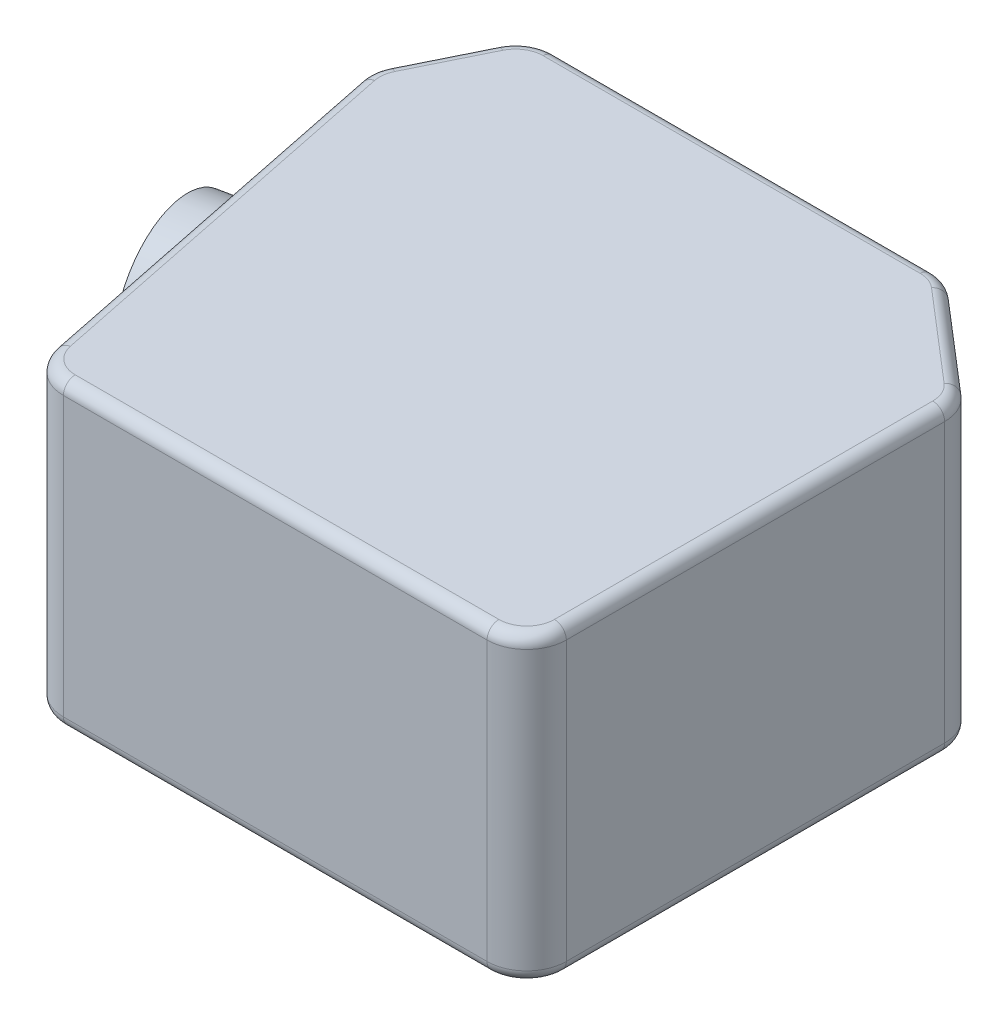
SolidWorks part; units mm, degrees
ref_plane "Front Plane" through (0, 0, 0) normal (0, 0, 1) x (1, 0, 0)
ref_plane "Top Plane" through (0, 0, 0) normal (0, 1, 0) x (1, 0, 0)
ref_plane "Right Plane" through (0, 0, 0) normal (1, 0, 0) x (0, 0, -1)
sketch "Sketch2" plane through (0, 0, 0) normal (0, 1, 0) x (1, 0, 0)
  line L0 (0, 0) -> (-22, 107.7775)
  line L1 (-22, 107.7775) -> (-8.7644, 134.7)
  line L2 (-8.7644, 134.7) -> (96.2356, 134.7)
  line L3 (96.2356, 134.7) -> (125, 110)
  line L4 (125, 110) -> (125, 0)
  line L5 (-55, 0) -> (55, 0) construction
  line L6 (125, 0) -> (0, 0)
  dimension "D1" = 134.7
  dimension "D2" = 147
  dimension "D3" = 125
  dimension "D4" = 105
  dimension "D5" = 110
  dimension "D6" = 110
  dimension "D7" = 30
  dimension "D8" = 37.9141
extrude "Boss-Extrude1" add sketch "Sketch2" along normal blind 76.2
sketch "Sketch3" plane through (0, 0, 0) normal (-0.9798, 0, 0.2) x (0.2, 0, 0.9798)
  line L0 (-110, 76.2) -> (0, 76.2) construction
  line L2 (-110, 76.2) -> (-110, 0) construction
  circle A0 centre (-77, 38.2) radius 20
  dimension "D1" = 40
  dimension "D2" = 38
  dimension "D3" = 33
extrude "Boss-Extrude2" add sketch "Sketch3" along normal blind 20
sketch "Sketch4" plane through (-19.5959, 0, 4) normal (-0.9798, 0, 0.2) x (0.2, 0, 0.9798)
  circle A0 centre (-77, 38.2) radius 15
  circle A1 centre (-77, 38.2) radius 20 construction
  dimension "D2" = 5
  dimension "D1" = 0
extrude "Cut-Extrude1" cut sketch "Sketch4" against normal blind 15
ref_plane "Plane1" through (0, -96.77, 0) normal (0, 1, 0) x (1, 0, 0)
sketch "Sketch6" plane through (0, -96.77, 0) normal (0, 1, 0) x (1, 0, 0)
  line L0 (-23.299, 89.1412) -> (-17.299, 59.7473) construction
  circle A0 centre (-20.299, 74.4443) radius 6.35
  dimension "D1" = 12.7
  dimension "D2" = 0
  dimension "D3" = 15
  dimension "D4" = 15
fillet "Fillet1" radius 10 6 edges at (96.2356, 38.1, -134.7) (-8.7644, 38.1, -134.7) (-22, 38.1, -107.7775) (125, 38.1, -110) (125, 38.1, 0) (0, 38.1, 0)
fillet "Fillet2" radius 3 24 edges at (-7.8234, 0, -133.1888) (-16.0023, 0, -119.9773) (-21.4374, 0, -107.7053) (-11.4749, 0, -56.2155) (1.8404, 0, -2.254) (61.5825, 0, 0) (122.0711, 0, -2.9289) (125, 0, -57.703) (124.087, 0, -109.5806) (110.2804, 0, -122.6398) (96.0049, 0, -134.0773) (44.9969, 0, -134.7) (124.087, 76.2, -109.5806) (125, 76.2, -57.703) (122.0711, 76.2, -2.9289) (61.5825, 76.2, 0) (1.8404, 76.2, -2.254) (-11.4749, 76.2, -56.2155) (-21.4374, 76.2, -107.7053) (-16.0023, 76.2, -119.9773) (-7.8234, 76.2, -133.1888) (44.9969, 76.2, -134.7) (96.0049, 76.2, -134.0773) (110.2804, 76.2, -122.6398)
shell "Shell1" thickness 5
equation "\"D5@Sketch2\"=\"D6@Sketch2\""
